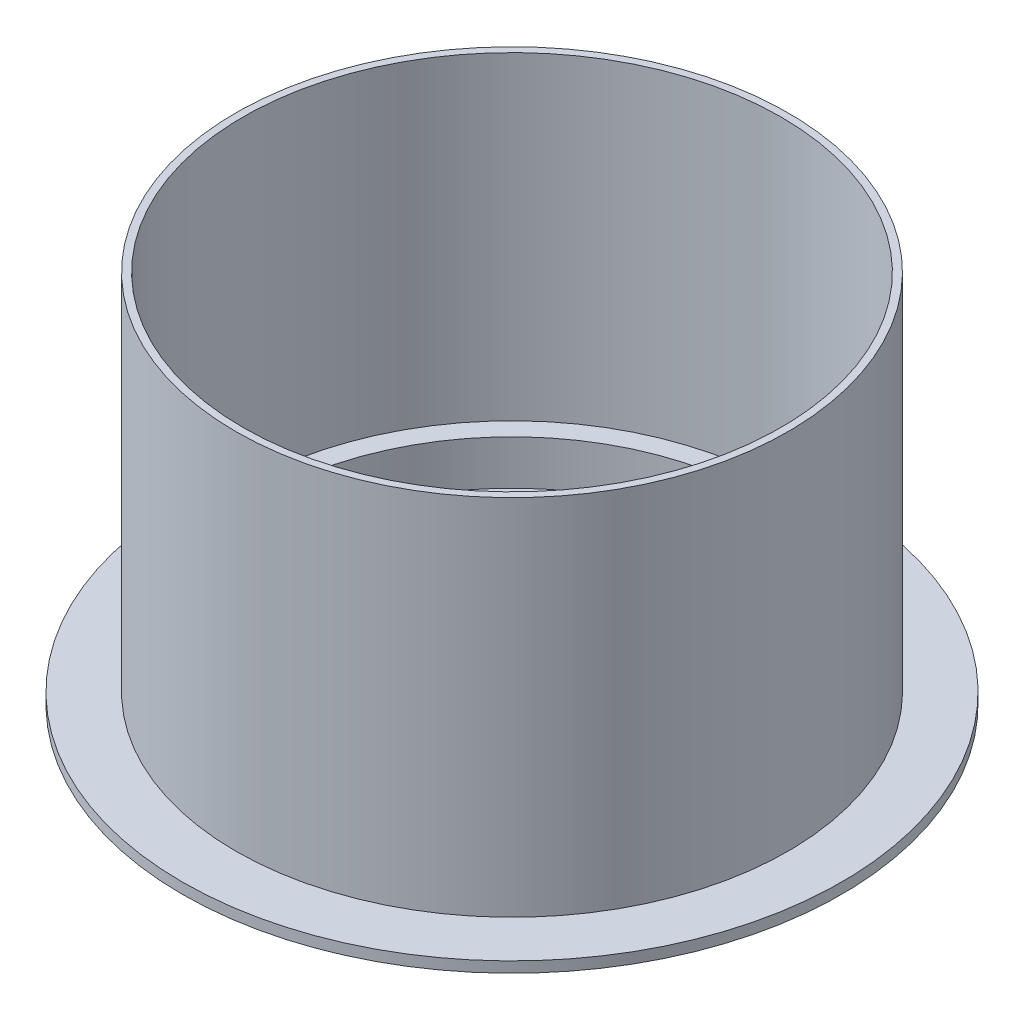
SolidWorks part; units mm, degrees
material "PE High Density"
ref_plane "Front Plane" through (0, 0, 0) normal (0, 0, 1) x (1, 0, 0)
ref_plane "Top Plane" through (0, 0, 0) normal (0, 1, 0) x (1, 0, 0)
ref_plane "Right Plane" through (0, 0, 0) normal (1, 0, 0) x (0, 0, -1)
sketch "Floor Sketch" plane through (0, 0, 0) normal (0, 1, 0) x (1, 0, 0)
  circle A0 centre (0, 0) radius 185
  circle A1 centre (0, 0) radius 12.5
  dimension "D1" = 370
  dimension "D2" = 25
extrude "Floor - Tank Lid" add sketch "Floor Sketch" along normal blind 6
sketch "Basket Ledge Sketch" plane through (0, 0, 0) normal (0, 1, 0) x (1, 0, 0)
  circle A0 centre (0, 0) radius 152
  circle A1 centre (0, 0) radius 140
  dimension "D1" = 304
  dimension "D2" = 280
extrude "Basket Ledge" add sketch "Basket Ledge Sketch" along normal blind 31
sketch "Housing Wall Sketch" plane through (0, 0, 0) normal (0, 1, 0) x (1, 0, 0)
  circle A0 centre (0, 0) radius 155
  circle A1 centre (0, 0) radius 151
  dimension "D1" = 310
  dimension "D2" = 302
extrude "Housing Wall" add sketch "Housing Wall Sketch" along normal blind 210
